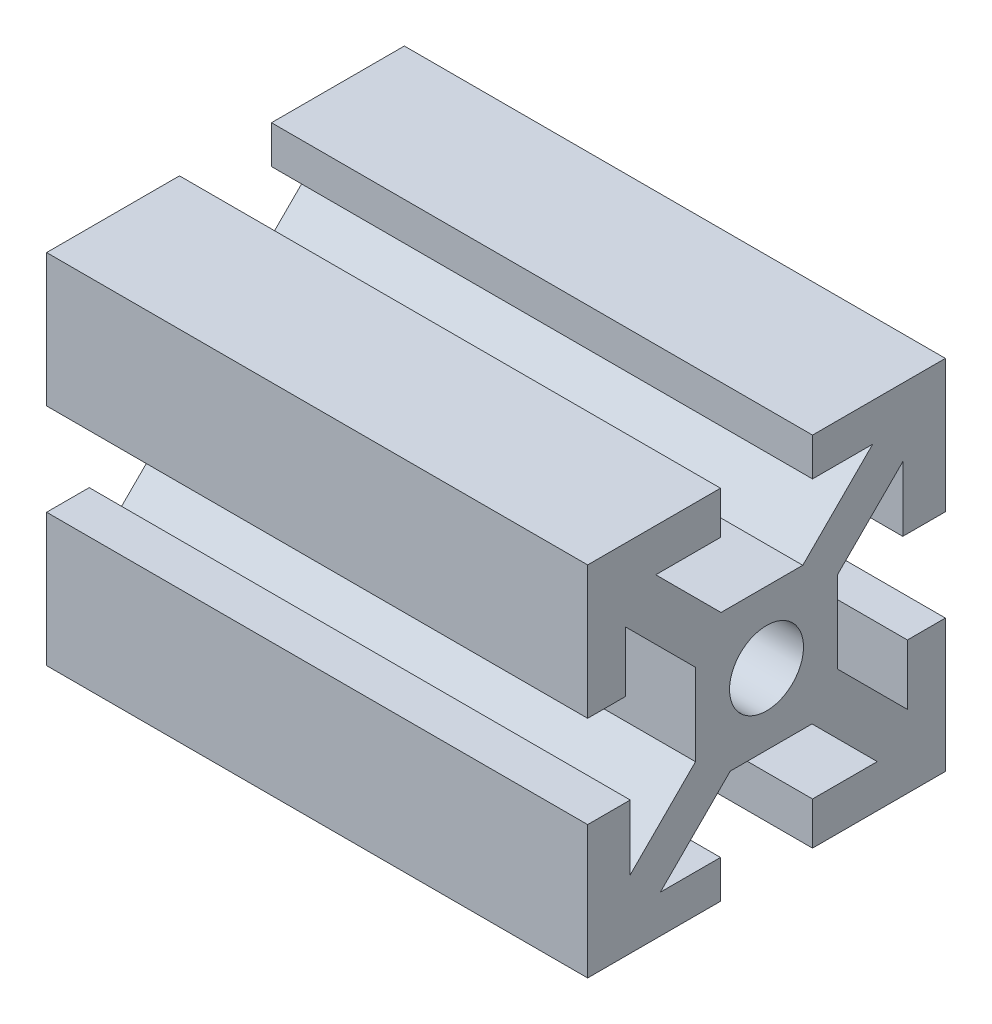
SolidWorks part; units mm, degrees
material "6061 Alloy"
ref_plane "Front Plane" through (0, 0, 0) normal (0, 0, 1) x (1, 0, 0)
ref_plane "Top Plane" through (0, 0, 0) normal (0, 1, 0) x (1, 0, 0)
ref_plane "Right Plane" through (0, 0, 0) normal (1, 0, 0) x (0, 0, -1)
sketch "Sketch1" plane through (0, 0, 0) normal (1, 0, 0) x (0, 0, -1)
  line L0 (2.5534, 5) -> (7.4749, 9.9215)
  line L1 (-5, 5) -> (5, 5)
  line L2 (-5, 5) -> (-5, -5)
  line L3 (-5, -5) -> (5, -5)
  line L4 (5, 5) -> (5, -5)
  line L5 (-5, 5) -> (5, -5) construction
  line L6 (-5, -5) -> (5, 5) construction
  line L7 (7.4749, 9.9215) -> (9.5962, 7.8001)
  line L8 (9.5962, 7.8001) -> (5, 3.2039)
  line L9 (5, 5) -> (13.6489, 13.6489) construction
  line L10 (7.4749, 9.9215) -> (3.24, 9.9215)
  line L11 (3.24, 9.9215) -> (3.24, 12.5962)
  line L12 (3.24, 12.5962) -> (12.5962, 12.5962)
  line L13 (9.5962, 7.8001) -> (9.5962, 3.24)
  line L14 (9.5962, 3.24) -> (12.5962, 3.24)
  line L15 (12.5962, 3.24) -> (12.5962, 12.5962)
  line L17 (0, 0) -> (0, 24.089) construction
  line L18 (0, 0) -> (23.75, 0) construction
  circle A0 centre (0, 0) radius 2.605
  point P0 (0, 0)
  dimension "D1" = 5.21
  dimension "D2" = 10
  dimension "D3" = 10
  dimension "D4" = 3
  dimension "D5" = 1.27
  dimension "D6" = 6.5
  dimension "D7" = 3.24
  dimension "D8" = 3.24
  dimension "D9" = 3
extrude "Boss-Extrude1" add sketch "Sketch1" along normal blind 38.1 contours L4 L1 L2 L3 A0 | L8 L7 L0 L1 L4 | L14 L15 L12 L11 L10 L7 L13 region at (0, 4.8586, -3.7767) region at (0, 6.7479, -6.3823) region at (0, 9.18, -9.3105)
ref_axis "Axis1" through (0, 0, 0) along (1, 0, 0)
pattern_circular "CirPattern1" count 4 over 360 about axis through (0, 0, 0) along (1, 0, 0) of "Boss-Extrude1"
